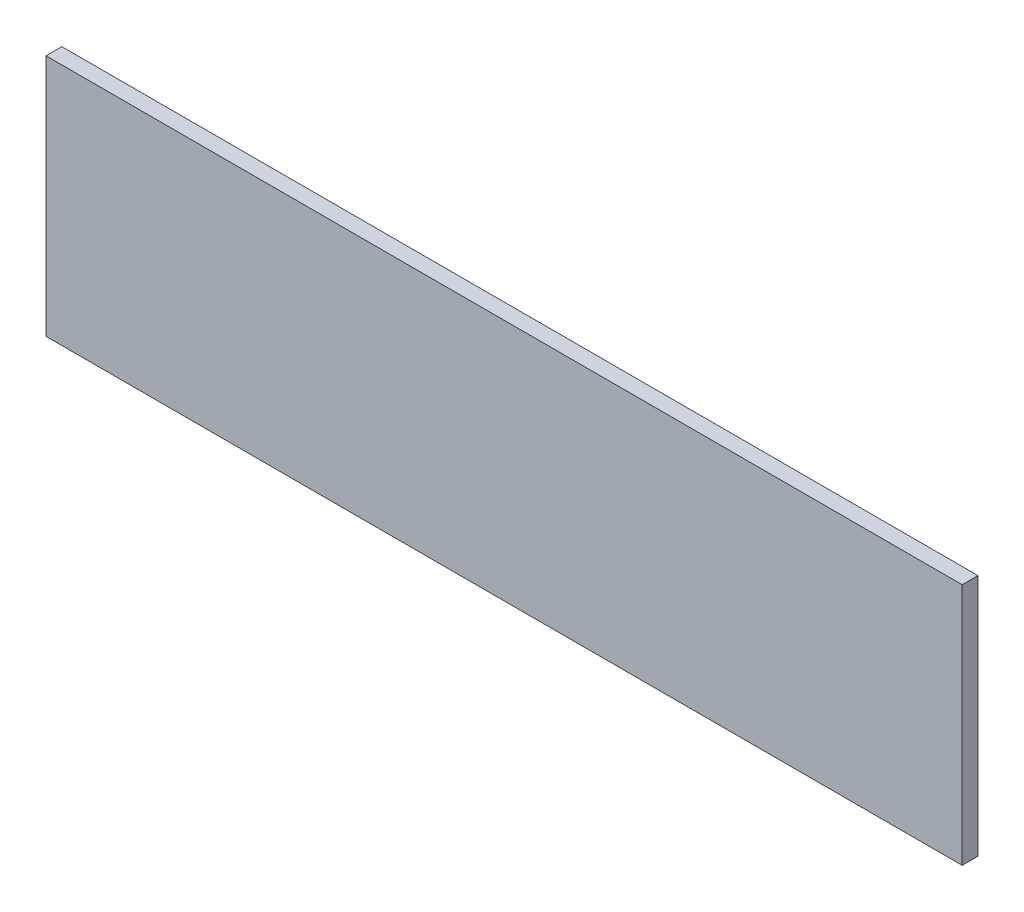
SolidWorks part; units mm, degrees
ref_plane "Plan de face" through (0, 0, 0) normal (0, 0, 1) x (1, 0, 0)
ref_plane "Plan de dessus" through (0, 0, 0) normal (0, 1, 0) x (1, 0, 0)
ref_plane "Plan de droite" through (0, 0, 0) normal (1, 0, 0) x (0, 0, -1)
sketch "Esquisse1" plane through (0, 0, 0) normal (0, 0, 1) x (1, 0, 0)
  line L1 (-139.4457, 100.7193) -> (237.5543, 100.7193)
  line L2 (-139.4457, 100.7193) -> (-139.4457, 0.7193)
  line L3 (-139.4457, 0.7193) -> (237.5543, 0.7193)
  line L4 (237.5543, 100.7193) -> (237.5543, 0.7193)
  dimension "D1" = 377
  dimension "D2" = 100
extrude "Boss.-Extru.1" add sketch "Esquisse1" along normal blind 6.5
